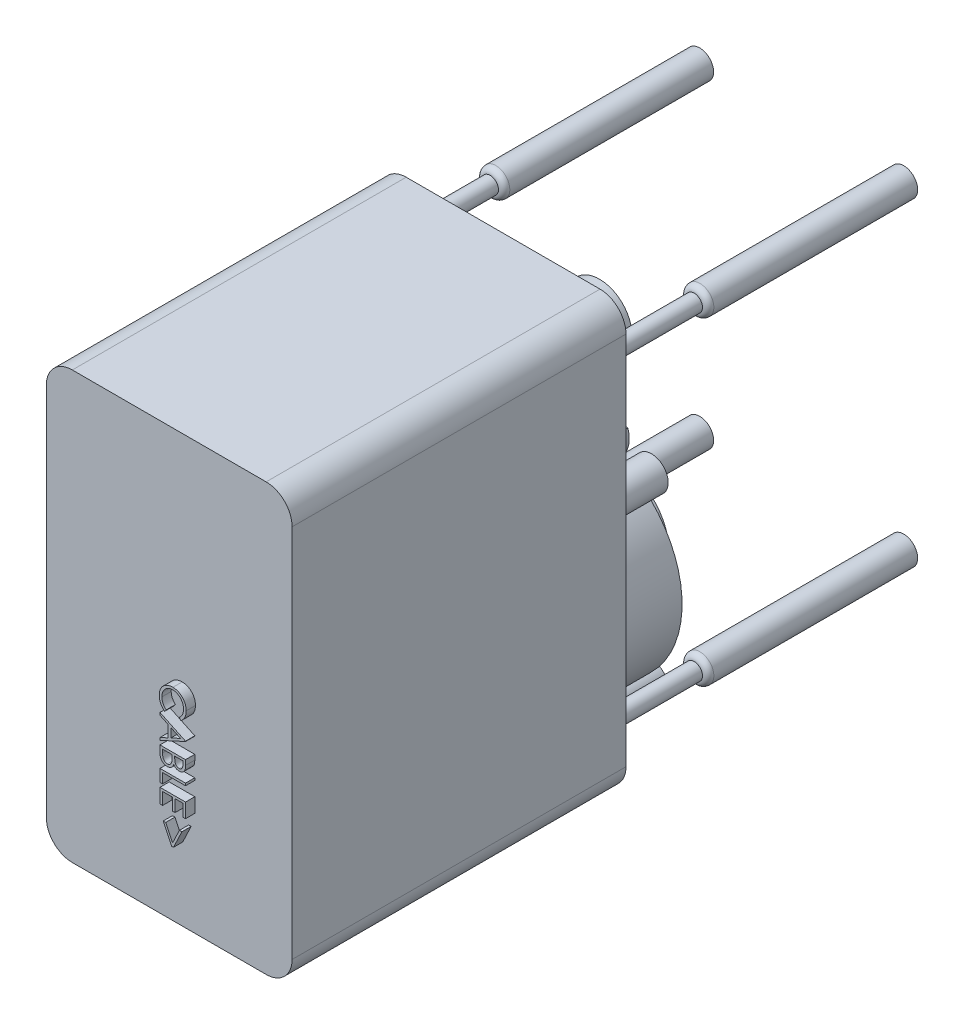
SolidWorks part; units mm, degrees
ref_plane "Front Plane" through (0, 0, 0) normal (0, 0, 1) x (1, 0, 0)
ref_plane "Top Plane" through (0, 0, 0) normal (0, 1, 0) x (1, 0, 0)
ref_plane "Right Plane" through (0, 0, 0) normal (1, 0, 0) x (0, 0, -1)
sketch "Sketch1" plane through (0, 0, 0) normal (0, 0, 1) x (1, 0, 0)
  line L0 (-13.081, 28.829) -> (13.081, 28.829)
  line L1 (-16.637, 25.273) -> (-16.637, -25.273)
  line L2 (-13.081, -28.829) -> (13.081, -28.829)
  line L3 (16.637, 25.273) -> (16.637, -25.273)
  line L4 (-16.637, 28.829) -> (16.637, -28.829) construction
  line L5 (-16.637, -28.829) -> (16.637, 28.829) construction
  line L6 (0, 36.9388) -> (0, -36.9388) construction
  line L7 (-21.0275, 0) -> (21.0275, 0) construction
  arc A0 (16.637, -25.273) -> (13.081, -28.829) centre (13.081, -25.273) cw
  arc A1 (-13.081, -28.829) -> (-16.637, -25.273) centre (-13.081, -25.273) cw
  arc A2 (16.637, 25.273) -> (13.081, 28.829) centre (13.081, 25.273) ccw
  arc A3 (-13.081, 28.829) -> (-16.637, 25.273) centre (-13.081, 25.273) ccw
  circle A4 centre (0, -12.7) radius 7.239
  circle A5 centre (0, 12.7) radius 4.445
  circle A6 centre (0, 14.605) radius 6.35
  circle A7 centre (0, -12.7) radius 14.351
  arc A8 (-3.6204, 1.1868) -> (3.6204, 1.1868) centre (0, 0) ccw
  circle A9 centre (13.97, 21.844) radius 1.016
  circle A10 centre (-13.97, 21.844) radius 1.016
  circle A11 centre (13.97, -21.844) radius 1.016
  circle A12 centre (-13.97, -21.844) radius 1.016
  arc A13 (6.6635, 0.0102) -> (10.0641, -2.4694) centre (8.89, -0.508) cw
  arc A14 (-10.0641, -2.4694) -> (-6.6635, 0.0102) centre (-8.89, -0.508) cw
  arc A15 (-10.0641, -22.9306) -> (-6.6635, -25.4102) centre (-8.89, -24.892) ccw
  arc A16 (6.6635, -25.4102) -> (10.0641, -22.9306) centre (8.89, -24.892) ccw
  point P0 (0, 0)
  dimension "D3" = 3.556
  dimension "D4" = 14.478
  dimension "D5" = 8.89
  dimension "D6" = 12.7
  dimension "D8" = 7.62
  dimension "D10" = 2.032
  dimension "D12" = 28.702
  dimension "D13" = 2.286
  dimension "D1" = 33.274
  dimension "D2" = 57.658
  dimension "D7" = 12.7
  dimension "D9" = 21.844
  dimension "D11" = 13.97
  dimension "D14" = 8.89
  dimension "D15" = 0.508
  dimension "D16" = 0.508
  dimension "D17" = 8.89
  dimension "D18" = 24.892
  dimension "D19" = 24.892
  dimension "D20" = 8.89
  dimension "D21" = 8.89
extrude "Boss-Extrude1" add sketch "Sketch1" against normal blind 10.16 contours A8 A7 A4 | A14 A7 | A7 A8 | A13 A7 | A7 A16 | A7 A15 | A4 region at (0, -12.7, 0) region at (12.8646, -18.0906, 0) region at (9.2197, -0.0559, 0) region at (9.2197, -25.3441, 0) region at (0, -0.8411, 0) region at (-9.2197, -25.3441, 0) region at (-9.2197, -0.0559, 0)
sketch "Sketch2" plane through (0, 0, 0) normal (0, 0, 1) x (1, 0, 0)
  line L0 (-13.081, 28.829) -> (13.081, 28.829)
  line L1 (-16.637, 25.273) -> (-16.637, -25.273)
  line L2 (-13.081, -28.829) -> (13.081, -28.829)
  line L3 (16.637, 25.273) -> (16.637, -25.273)
  line L4 (-16.637, 28.829) -> (16.637, -28.829) construction
  line L5 (-16.637, -28.829) -> (16.637, 28.829) construction
  line L6 (0, 38.9705) -> (0, -34.9071) construction
  line L7 (-9.8575, 0) -> (32.1974, 0) construction
  arc A0 (16.637, -25.273) -> (13.081, -28.829) centre (13.081, -25.273) cw
  arc A1 (-13.081, -28.829) -> (-16.637, -25.273) centre (-13.081, -25.273) cw
  arc A2 (16.637, 25.273) -> (13.081, 28.829) centre (13.081, 25.273) ccw
  arc A3 (-13.081, 28.829) -> (-16.637, 25.273) centre (-13.081, 25.273) ccw
  circle A4 centre (0, -12.7) radius 7.239
  circle A5 centre (0, 12.7) radius 4.445
  circle A6 centre (0, 14.605) radius 6.35
  circle A7 centre (0, -12.7) radius 14.351
  arc A8 (-3.6204, 1.1868) -> (3.6204, 1.1868) centre (0, 0) ccw
  circle A9 centre (13.97, 21.844) radius 1.016
  circle A10 centre (-13.97, 21.844) radius 1.016
  circle A11 centre (13.97, -21.844) radius 1.016
  circle A12 centre (-13.97, -21.844) radius 1.016
  arc A13 (6.6635, 0.0102) -> (10.0641, -2.4694) centre (8.89, -0.508) cw
  arc A14 (-10.0641, -2.4694) -> (-6.6635, 0.0102) centre (-8.89, -0.508) cw
  arc A15 (-10.0641, -22.9306) -> (-6.6635, -25.4102) centre (-8.89, -24.892) ccw
  arc A16 (6.6635, -25.4102) -> (10.0641, -22.9306) centre (8.89, -24.892) ccw
  point P0 (0, 0)
  dimension "D3" = 3.556
  dimension "D4" = 14.478
  dimension "D5" = 8.89
  dimension "D6" = 12.7
  dimension "D8" = 7.62
  dimension "D10" = 2.032
  dimension "D12" = 28.702
  dimension "D13" = 2.286
  dimension "D1" = 33.274
  dimension "D2" = 57.658
  dimension "D7" = 12.7
  dimension "D9" = 21.844
  dimension "D11" = 13.97
  dimension "D14" = 8.89
  dimension "D15" = 0.508
  dimension "D16" = 0.508
  dimension "D17" = 8.89
  dimension "D18" = 24.892
  dimension "D19" = 24.892
  dimension "D20" = 8.89
  dimension "D21" = 8.89
extrude "Boss-Extrude2" add sketch "Sketch2" against normal blind 1.778 separate body contours A5 | A5 A6 region at (0, 12.7, 0) region at (-4.3631, 18.9681, 0)
sketch "Sketch3" plane through (0, 0, -10.16) normal (0, 0, -1) x (-1, 0, 0)
  circle A0 centre (-8.89, -0.508) radius 2.286
  circle A1 centre (8.89, -24.892) radius 2.286
  circle A2 centre (-8.89, -24.892) radius 2.286
  circle A3 centre (8.89, -0.508) radius 2.286
extrude "Boss-Extrude3" add sketch "Sketch3" along normal blind 1.27
sketch "Sketch4" plane through (0, 0, -10.16) normal (0, 0, -1) x (-1, 0, 0)
  line L0 (-13.081, 28.829) -> (13.081, 28.829)
  line L1 (-16.637, 25.273) -> (-16.637, -25.273)
  line L2 (-13.081, -28.829) -> (13.081, -28.829)
  line L3 (16.637, 25.273) -> (16.637, -25.273)
  line L4 (-16.637, 28.829) -> (16.637, -28.829) construction
  line L5 (-16.637, -28.829) -> (16.637, 28.829) construction
  line L6 (0, 23.9866) -> (0, -49.891) construction
  line L7 (7.1619, 0) -> (49.2169, 0) construction
  arc A0 (16.637, -25.273) -> (13.081, -28.829) centre (13.081, -25.273) cw
  arc A1 (-13.081, -28.829) -> (-16.637, -25.273) centre (-13.081, -25.273) cw
  arc A2 (16.637, 25.273) -> (13.081, 28.829) centre (13.081, 25.273) ccw
  arc A3 (-13.081, 28.829) -> (-16.637, 25.273) centre (-13.081, 25.273) ccw
  circle A4 centre (0, -12.7) radius 7.239
  circle A5 centre (0, 12.7) radius 4.445
  circle A6 centre (0, 14.605) radius 6.35
  circle A7 centre (0, -12.7) radius 14.351
  arc A8 (-3.6204, 1.1868) -> (3.6204, 1.1868) centre (0, 0) ccw
  circle A9 centre (13.97, 21.844) radius 1.016
  circle A10 centre (-13.97, 21.844) radius 1.016
  circle A11 centre (13.97, -21.844) radius 1.016
  circle A12 centre (-13.97, -21.844) radius 1.016
  arc A13 (6.6635, 0.0102) -> (10.0641, -2.4694) centre (8.89, -0.508) cw
  arc A14 (-10.0641, -2.4694) -> (-6.6635, 0.0102) centre (-8.89, -0.508) cw
  arc A15 (-10.0641, -22.9306) -> (-6.6635, -25.4102) centre (-8.89, -24.892) ccw
  arc A16 (6.6635, -25.4102) -> (10.0641, -22.9306) centre (8.89, -24.892) ccw
  point P0 (0, 0)
  dimension "D3" = 3.556
  dimension "D4" = 14.478
  dimension "D5" = 8.89
  dimension "D6" = 12.7
  dimension "D8" = 7.62
  dimension "D10" = 2.032
  dimension "D12" = 28.702
  dimension "D13" = 2.286
  dimension "D1" = 33.274
  dimension "D2" = 57.658
  dimension "D7" = 12.7
  dimension "D9" = 21.844
  dimension "D11" = 13.97
  dimension "D14" = 8.89
  dimension "D15" = 0.508
  dimension "D16" = 0.508
  dimension "D17" = 8.89
  dimension "D18" = 24.892
  dimension "D19" = 24.892
  dimension "D20" = 8.89
  dimension "D21" = 8.89
extrude "Boss-Extrude4" add sketch "Sketch4" along normal blind 3.302 contours A7 A8 region at (0, -0.8411, -10.16)
sketch "Sketch5" plane through (0, 0, -1.778) normal (0, 0, -1) x (-1, 0, 0)
  line L0 (-13.081, 28.829) -> (13.081, 28.829)
  line L1 (-16.637, 25.273) -> (-16.637, -25.273)
  line L2 (-13.081, -28.829) -> (13.081, -28.829)
  line L3 (16.637, 25.273) -> (16.637, -25.273)
  line L4 (-16.637, 28.829) -> (16.637, -28.829) construction
  line L5 (-16.637, -28.829) -> (16.637, 28.829) construction
  line L6 (0, 36.0331) -> (0, -37.8445) construction
  line L7 (26.8703, 0) -> (68.9252, 0) construction
  arc A0 (16.637, -25.273) -> (13.081, -28.829) centre (13.081, -25.273) cw
  arc A1 (-13.081, -28.829) -> (-16.637, -25.273) centre (-13.081, -25.273) cw
  arc A2 (16.637, 25.273) -> (13.081, 28.829) centre (13.081, 25.273) ccw
  arc A3 (-13.081, 28.829) -> (-16.637, 25.273) centre (-13.081, 25.273) ccw
  circle A4 centre (0, -12.7) radius 7.239
  circle A5 centre (0, 12.7) radius 4.445
  circle A6 centre (0, 14.605) radius 6.35
  circle A7 centre (0, -12.7) radius 14.351
  arc A8 (-3.6204, 1.1868) -> (3.6204, 1.1868) centre (0, 0) ccw
  circle A9 centre (13.97, 21.844) radius 1.016
  circle A10 centre (-13.97, 21.844) radius 1.016
  circle A11 centre (13.97, -21.844) radius 1.016
  circle A12 centre (-13.97, -21.844) radius 1.016
  arc A13 (6.6635, 0.0102) -> (10.0641, -2.4694) centre (8.89, -0.508) cw
  arc A14 (-10.0641, -2.4694) -> (-6.6635, 0.0102) centre (-8.89, -0.508) cw
  arc A15 (-10.0641, -22.9306) -> (-6.6635, -25.4102) centre (-8.89, -24.892) ccw
  arc A16 (6.6635, -25.4102) -> (10.0641, -22.9306) centre (8.89, -24.892) ccw
  point P0 (0, 0)
  dimension "D3" = 3.556
  dimension "D4" = 14.478
  dimension "D5" = 8.89
  dimension "D6" = 12.7
  dimension "D8" = 7.62
  dimension "D10" = 2.032
  dimension "D12" = 28.702
  dimension "D13" = 2.286
  dimension "D1" = 33.274
  dimension "D2" = 57.658
  dimension "D7" = 12.7
  dimension "D9" = 21.844
  dimension "D11" = 13.97
  dimension "D14" = 8.89
  dimension "D15" = 0.508
  dimension "D16" = 0.508
  dimension "D17" = 8.89
  dimension "D18" = 24.892
  dimension "D19" = 24.892
  dimension "D20" = 8.89
  dimension "D21" = 8.89
extrude "Boss-Extrude5" add sketch "Sketch5" along normal blind 11.43 contours A5 region at (0, 12.7, -1.778)
sketch "Sketch6" plane through (0, 0, 0) normal (0, 0, 1) x (1, 0, 0)
  line L0 (-13.081, 28.829) -> (13.081, 28.829)
  line L1 (-16.637, 25.273) -> (-16.637, -25.273)
  line L2 (-13.081, -28.829) -> (13.081, -28.829)
  line L3 (16.637, 25.273) -> (16.637, -25.273)
  line L4 (-16.637, 28.829) -> (16.637, -28.829) construction
  line L5 (-16.637, -28.829) -> (16.637, 28.829) construction
  line L6 (0, 36.0885) -> (0, -37.789) construction
  line L7 (-47.9194, 0) -> (-5.8644, 0) construction
  arc A0 (16.637, -25.273) -> (13.081, -28.829) centre (13.081, -25.273) cw
  arc A1 (-13.081, -28.829) -> (-16.637, -25.273) centre (-13.081, -25.273) cw
  arc A2 (16.637, 25.273) -> (13.081, 28.829) centre (13.081, 25.273) ccw
  arc A3 (-13.081, 28.829) -> (-16.637, 25.273) centre (-13.081, 25.273) ccw
  circle A4 centre (0, -12.7) radius 7.239
  circle A5 centre (0, 12.7) radius 4.445
  circle A6 centre (0, 14.605) radius 6.35
  circle A7 centre (0, -12.7) radius 14.351
  arc A8 (-3.6204, 1.1868) -> (3.6204, 1.1868) centre (0, 0) ccw
  circle A9 centre (13.97, 21.844) radius 1.143
  circle A10 centre (-13.97, 21.844) radius 1.143
  circle A11 centre (13.97, -21.844) radius 1.143
  circle A12 centre (-13.97, -21.844) radius 1.143
  arc A13 (6.6635, 0.0102) -> (10.0641, -2.4694) centre (8.89, -0.508) cw
  arc A14 (-10.0641, -2.4694) -> (-6.6635, 0.0102) centre (-8.89, -0.508) cw
  arc A15 (-10.0641, -22.9306) -> (-6.6635, -25.4102) centre (-8.89, -24.892) ccw
  arc A16 (6.6635, -25.4102) -> (10.0641, -22.9306) centre (8.89, -24.892) ccw
  point P0 (0, 0)
  dimension "D3" = 3.556
  dimension "D4" = 14.478
  dimension "D5" = 8.89
  dimension "D6" = 12.7
  dimension "D8" = 7.62
  dimension "D10" = 2.286
  dimension "D12" = 28.702
  dimension "D13" = 2.286
  dimension "D1" = 33.274
  dimension "D2" = 57.658
  dimension "D7" = 12.7
  dimension "D9" = 21.844
  dimension "D11" = 13.97
  dimension "D14" = 8.89
  dimension "D15" = 0.508
  dimension "D16" = 0.508
  dimension "D17" = 8.89
  dimension "D18" = 24.892
  dimension "D19" = 24.892
  dimension "D20" = 8.89
  dimension "D21" = 8.89
extrude "Boss-Extrude6" add sketch "Sketch6" against normal blind 15.494 separate body contours A10 | A9 | A12 | A11 region at (13.97, 21.844, 0) region at (-13.97, 21.844, 0) region at (13.97, -21.844, 0) region at (-13.97, -21.844, 0)
sketch "Sketch7" plane through (0, 0, -10.16) normal (0, 0, -1) x (-1, 0, 0)
  line L0 (-13.081, 28.829) -> (13.081, 28.829)
  line L1 (-16.637, 25.273) -> (-16.637, -25.273)
  line L2 (-13.081, -28.829) -> (13.081, -28.829)
  line L3 (16.637, 25.273) -> (16.637, -25.273)
  line L4 (-16.637, 28.829) -> (16.637, -28.829) construction
  line L5 (-16.637, -28.829) -> (16.637, 28.829) construction
  line L6 (0, 26.9541) -> (0, -46.9235) construction
  line L7 (8.0915, 0) -> (50.1464, 0) construction
  arc A0 (16.637, -25.273) -> (13.081, -28.829) centre (13.081, -25.273) cw
  arc A1 (-13.081, -28.829) -> (-16.637, -25.273) centre (-13.081, -25.273) cw
  arc A2 (16.637, 25.273) -> (13.081, 28.829) centre (13.081, 25.273) ccw
  arc A3 (-13.081, 28.829) -> (-16.637, 25.273) centre (-13.081, 25.273) ccw
  circle A4 centre (0, -12.7) radius 7.239
  circle A5 centre (0, 12.7) radius 4.445
  circle A6 centre (0, 14.605) radius 6.35
  circle A7 centre (0, -12.7) radius 14.351
  arc A8 (-3.6204, 1.1868) -> (3.6204, 1.1868) centre (0, 0) ccw
  circle A9 centre (13.97, 21.844) radius 1.016
  circle A10 centre (-13.97, 21.844) radius 1.016
  circle A11 centre (13.97, -21.844) radius 1.016
  circle A12 centre (-13.97, -21.844) radius 1.016
  arc A13 (6.6635, 0.0102) -> (10.0641, -2.4694) centre (8.89, -0.508) cw
  arc A14 (-10.0641, -2.4694) -> (-6.6635, 0.0102) centre (-8.89, -0.508) cw
  arc A15 (-10.0641, -22.9306) -> (-6.6635, -25.4102) centre (-8.89, -24.892) ccw
  arc A16 (6.6635, -25.4102) -> (10.0641, -22.9306) centre (8.89, -24.892) ccw
  point P0 (0, 0)
  dimension "D3" = 3.556
  dimension "D4" = 14.478
  dimension "D5" = 8.89
  dimension "D6" = 12.7
  dimension "D8" = 7.62
  dimension "D10" = 2.032
  dimension "D12" = 28.702
  dimension "D13" = 2.286
  dimension "D1" = 33.274
  dimension "D2" = 57.658
  dimension "D7" = 12.7
  dimension "D9" = 21.844
  dimension "D11" = 13.97
  dimension "D14" = 8.89
  dimension "D15" = 0.508
  dimension "D16" = 0.508
  dimension "D17" = 8.89
  dimension "D18" = 24.892
  dimension "D19" = 24.892
  dimension "D20" = 8.89
  dimension "D21" = 8.89
extrude "Boss-Extrude7" add sketch "Sketch7" along normal blind 5.334 contours A4 region at (0, -12.7, -10.16)
sketch "Sketch8" plane through (0, 0, 0) normal (0, 0, 1) x (1, 0, 0)
  line L1 (-13.2715, 29.21) -> (13.2715, 29.21)
  line L2 (-16.8275, 25.654) -> (-16.8275, -25.654)
  line L3 (-13.2715, -29.21) -> (13.2715, -29.21)
  line L4 (16.8275, 25.654) -> (16.8275, -25.654)
  line L5 (-16.8275, 29.21) -> (16.8275, -29.21) construction
  line L6 (-16.8275, -29.21) -> (16.8275, 29.21) construction
  arc A8 (16.8275, -25.654) -> (13.2715, -29.21) centre (13.2715, -25.654) cw
  arc A13 (-13.2715, -29.21) -> (-16.8275, -25.654) centre (-13.2715, -25.654) cw
  arc A14 (16.8275, 25.654) -> (13.2715, 29.21) centre (13.2715, 25.654) ccw
  arc A15 (-13.2715, 29.21) -> (-16.8275, 25.654) centre (-13.2715, 25.654) ccw
  point P0 (0, 0)
  dimension "D3" = 3.556
  dimension "D1" = 33.655
  dimension "D23" = 58.42
extrude "Boss-Extrude8" add sketch "Sketch8" along normal blind 45.72
sketch "Sketch9" plane through (0, 0, -15.494) normal (0, 0, -1) x (-1, 0, 0)
  circle A0 centre (-13.97, 21.844) radius 1.905
  circle A1 centre (13.97, 21.844) radius 1.905
  circle A2 centre (13.97, -21.844) radius 1.905
  circle A3 centre (-13.97, -21.844) radius 1.905
  dimension "D1" = 3.81
extrude "Boss-Extrude9" add sketch "Sketch9" against normal blind 3.302 and the other way blind 25.4
sketch "Sketch10" plane through (0, 0, 45.72) normal (0, 0, 1) x (1, 0, 0)
  line L0 (0, 0) -> (0, -29.21) construction
  line L1 (-13.2715, -29.21) -> (13.2715, -29.21) construction
  text T0 "CABLE >"
extrude "Boss-Extrude10" add sketch "Sketch10" along normal blind 1.27
fillet "Fillet1" radius 0.7937 4 edges at (-15.875, -21.844, -12.192) (12.065, -21.844, -12.192) (12.065, 21.844, -12.192) (-15.875, 21.844, -12.192)
